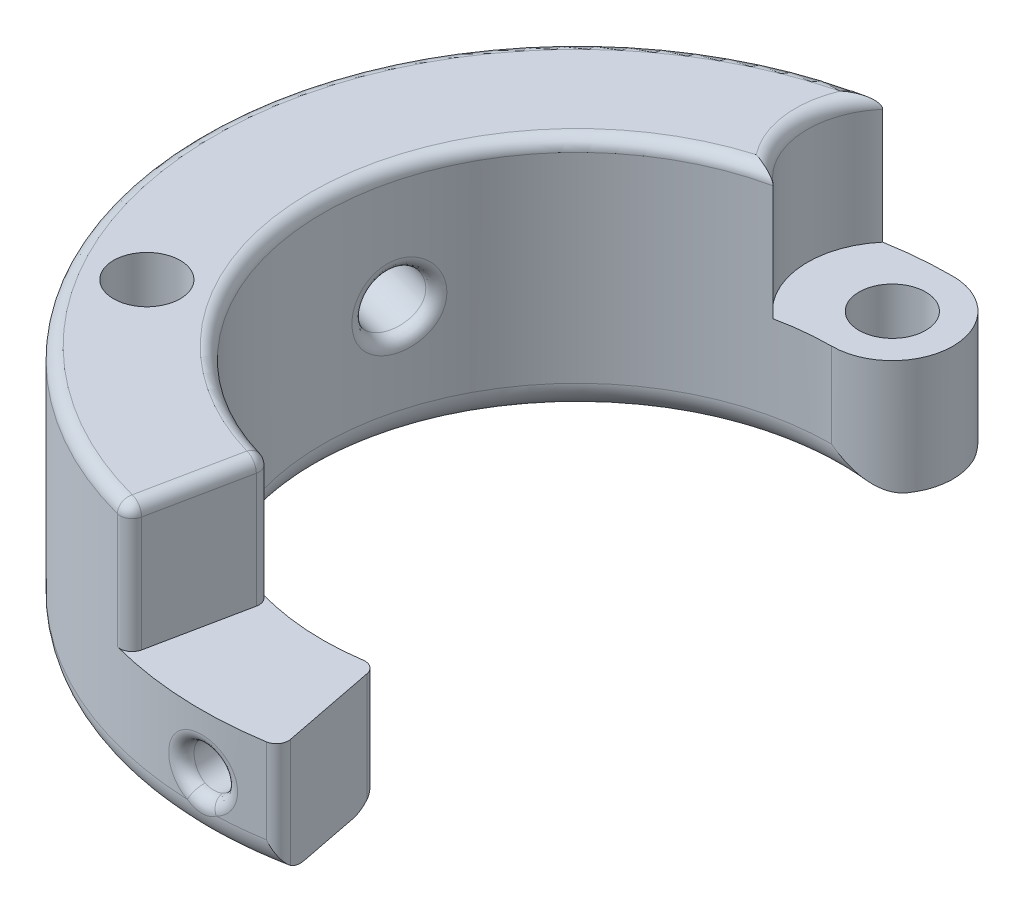
SolidWorks part; units mm, degrees
ref_plane "Front Plane" through (0, 0, 0) normal (0, 0, 1) x (1, 0, 0)
ref_plane "Top Plane" through (0, 0, 0) normal (0, 1, 0) x (1, 0, 0)
ref_plane "Right Plane" through (0, 0, 0) normal (1, 0, 0) x (0, 0, -1)
sketch "Sketch1" plane through (0, 0, 0) normal (0, 1, 0) x (1, 0, 0)
  line L0 (0, 31) -> (29.9823, 31) construction
  line L1 (0, 0) -> (0, 26) construction
  line L2 (0, 0) -> (-22.5167, -13) construction
  line L3 (4.2264, -21.567) -> (5.766, -29.4237)
  line L4 (0, 0) -> (4.0385, -20.608) construction
  circle A0 centre (0, 26) radius 2.75
  arc A1 (0, 31) -> (0, 21) centre (0, 26) cw
  arc A2 (0, 31) -> (0, -31) centre (0, 0) ccw
  arc A3 (0, 21) -> (0, -21) centre (0, 0) ccw
  arc A4 (0, -21) -> (0, -31) centre (0, -26) cw construction
  circle A5 centre (-22.5167, -13) radius 2.75
  arc A6 (0, -21) -> (3.0976, -20.7703) centre (0, 0) ccw
  arc A7 (0, -31) -> (4.9442, -30.6032) centre (0, 0) ccw
  arc A8 (4.9442, -30.6032) -> (5.766, -29.4237) centre (4.7847, -29.616) ccw
  arc A9 (3.0976, -20.7703) -> (4.2264, -21.567) centre (3.2451, -21.7594) cw
  dimension "D1" = 5.5
  dimension "D7" = 1
  dimension "D2" = 10
  dimension "D3" = 21
  dimension "D5" = 120
  dimension "D6" = 26
  dimension "D4" = 2
extrude "Boss-Extrude1" add sketch "Sketch1" along normal blind 20
sketch "Sketch3" plane through (0, 0, 0) normal (0, 0, 1) x (1, 0, 0)
  line L0 (4.9442, 20) -> (-31, 20) construction
  circle A0 centre (0, 15) radius 1.75
  circle A1 centre (0, 5) radius 1.75
  dimension "D1" = 3.5
  dimension "D4" = 3.5
  dimension "D2" = 5
  dimension "D3" = 5
extrude "Cut-Extrude2" cut sketch "Sketch3" along normal blind 71
sketch "Sketch2" plane through (0, 20, 0) normal (0, 1, 0) x (1, 0, 0)
  line L0 (0, -1000) -> (0, 49000) construction
  line L1 (5.766, -29.4237) -> (4.2264, -21.567)
  line L2 (5.766, -29.4237) -> (4.2264, -21.567) construction
  line L3 (-5.766, -29.4237) -> (-4.2264, -21.567) construction
  line L4 (-4.0385, -20.608) -> (0, 0) construction
  line L5 (0, 0) -> (-3.149, 20.5458) construction
  line L6 (0, 26) -> (-4.3301, 28.5) construction
  line L7 (0, 26) -> (-22.5167, -13) construction
  line L10 (-4.3301, 28.5) -> (-14.6574, 34.4625) construction
  line L11 (-3.1815, 20.7576) -> (-3.0168, 19.6835) construction
  line L12 (-3.1815, 20.7576) -> (-3.0168, 19.6835)
  line L13 (-3.149, 20.5458) -> (-3.1815, 20.7576) construction
  line L17 (-4.7701, 31.1231) -> (-4.6964, 30.6422)
  line L18 (-4.971, -20.4032) -> (-6.9723, -30.2058)
  arc A0 (0, 31) -> (0, 21) centre (0, 26) ccw construction
  arc A1 (-4.7701, 31.1231) -> (-3.0168, 19.6835) centre (0, 26) ccw
  arc A2 (0, 33) -> (0, 19) centre (0, 26) ccw construction
  arc A3 (0, 21) -> (-4.3785, 20.5385) centre (0, 0) ccw construction
  arc A5 (0, 31) -> (4.9442, -30.6032) centre (0, 0) ccw
  arc A6 (4.9442, -30.6032) -> (5.766, -29.4237) centre (4.7847, -29.616) ccw
  arc A7 (4.2264, -21.567) -> (3.0976, -20.7703) centre (3.2451, -21.7594) ccw
  arc A8 (0, 21) -> (3.0976, -20.7703) centre (0, 0) ccw
  arc A9 (0, 21) -> (0, 31) centre (0, 26) ccw
  arc A10 (-4.6964, 30.6422) -> (-6.9723, -30.2058) centre (0, 0) ccw construction
  arc A11 (4.9442, -30.6032) -> (5.766, -29.4237) centre (4.7847, -29.616) ccw construction
  arc A12 (4.2264, -21.567) -> (3.0976, -20.7703) centre (3.2451, -21.7594) ccw construction
  arc A13 (-3.3375, 20.7331) -> (-4.971, -20.4032) centre (0, 0) ccw construction
  arc A16 (-4.0385, -20.608) -> (0, -21) centre (0, 0) ccw construction
  arc A17 (0, -21) -> (3.0976, -20.7703) centre (0, 0) ccw construction
  arc A18 (0, -31) -> (4.9442, -30.6032) centre (0, 0) ccw construction
  arc A19 (-5.9615, -30.4214) -> (0, -31) centre (0, 0) ccw construction
  arc A20 (-5.766, -29.4237) -> (-6.9723, -30.2058) centre (-6.7474, -29.2314) cw construction
  arc A21 (-4.2264, -21.567) -> (-4.971, -20.4032) centre (-5.2077, -21.3747) ccw construction
  arc A22 (0, 31) -> (-6.9723, -30.2058) centre (0, 0) cw
  arc A23 (-4.971, -20.4032) -> (-3.1815, 20.7576) centre (0, 0) ccw
  arc A24 (0, 31) -> (4.9442, -30.6032) centre (0, 0) ccw construction
  arc A25 (-1.3518, 32.8682) -> (-4.7701, 31.1231) centre (0, 26) ccw construction
  circle M14 centre (0, 26) radius 2.75
  arc M15 (0, 31) -> (4.9442, -30.6032) centre (0, 0) ccw
  arc M16 (4.9442, -30.6032) -> (5.766, -29.4237) centre (4.7847, -29.616) ccw
  line M17 (5.766, -29.4237) -> (4.2264, -21.567)
  arc M18 (4.2264, -21.567) -> (3.0976, -20.7703) centre (3.2451, -21.7594) ccw
  arc M19 (3.0976, -20.7703) -> (0, 21) centre (0, 0) cw
  arc M20 (0, 21) -> (0, 31) centre (0, 26) ccw
  dimension "D4" = 1
  dimension "D1" = 0
  dimension "D2" = 2
extrude "Cut-Extrude1" cut sketch "Sketch2" against normal blind 10.5 contours L18 M19 M15 M16 M17 M18 | A23 A22 M18 M17 M16 M20 | L17 A1 L12 M19 M20 M15 M14 region at (-0.5151, 20, 26.0965) region at (5.673, 20, 25.3627) region at (4.8408, 20, -26)
sketch "Sketch4" plane through (0, 0, 0) normal (0, -1, 0) x (1, 0, 0)
  circle A0 centre (0, -26) radius 2.75 construction
  circle A1 centre (-22.5167, 13) radius 2.75 construction
  circle A2 centre (0, -26) radius 2.75
  circle A3 centre (-22.5167, 13) radius 2.75
extrude "Boss-Extrude2" add sketch "Sketch4" against normal blind 3
fillet "Fillet1" radius 2.5 2 edges at (-30.9006, 0, 2.48) (-20.9425, 0, 1.553) tangent propagation no
fillet "Fillet2" radius 1 6 edges at (-6.9686, 20, -25.3374) (-4.971, 14.75, 20.4032) (-6.9723, 14.75, 30.2058) (-20.9978, 20, -0.3039) (-5.9716, 20, 25.3045) (-30.9887, 20, -0.8381)
ref_plane "Plane1" through (-20.2844, 0, -5.4352) normal (0.9659, 0, 0.2588) x (0, -1, 0)
sketch "Sketch5" plane through (-22.1916, 0, 1.6823) normal (0.9659, 0, 0.2588) x (0.2588, 0, -0.9659)
  circle A0 centre (7.3686, 10) radius 2.35
  dimension "D2" = 4.7
  dimension "D1" = 10
extrude "Cut-Extrude3" cut sketch "Sketch5" against normal through all both and the other way through all
fillet "Fillet3" radius 1 4 edges at (-30.4544, 9.4671, -5.7907) (-20.7563, 10.524, -3.19) (1.7038, 5.3994, 30.9531) (1.7047, 4.6043, 20.9307)
